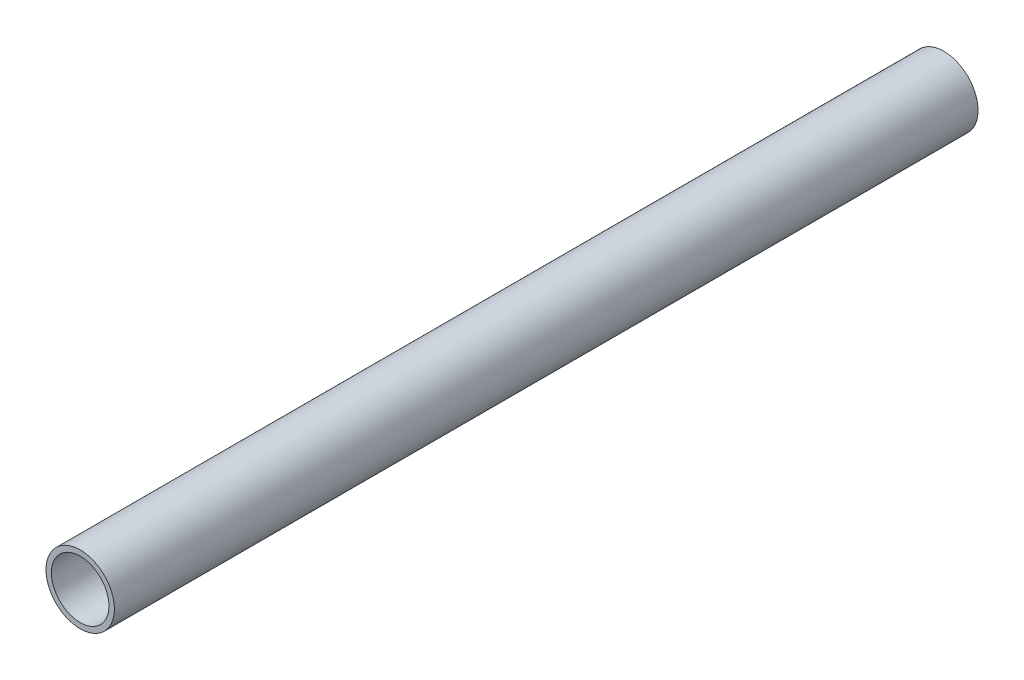
SolidWorks part; units mm, degrees
ref_plane "Front Plane" through (0, 0, 0) normal (0, 0, 1) x (1, 0, 0)
ref_plane "Top Plane" through (0, 0, 0) normal (0, 1, 0) x (1, 0, 0)
ref_plane "Right Plane" through (0, 0, 0) normal (1, 0, 0) x (0, 0, -1)
sketch "Sketch1" plane through (0, 0, 0) normal (0, 0, 1) x (1, 0, 0)
  circle A0 centre (0, 0) radius 20.32
  circle A1 centre (0, 0) radius 24.13
  dimension "D1" = 40.64
  dimension "D2" = 48.26
extrude "Boss-Extrude1" add sketch "Sketch1" along normal blind 609.6
